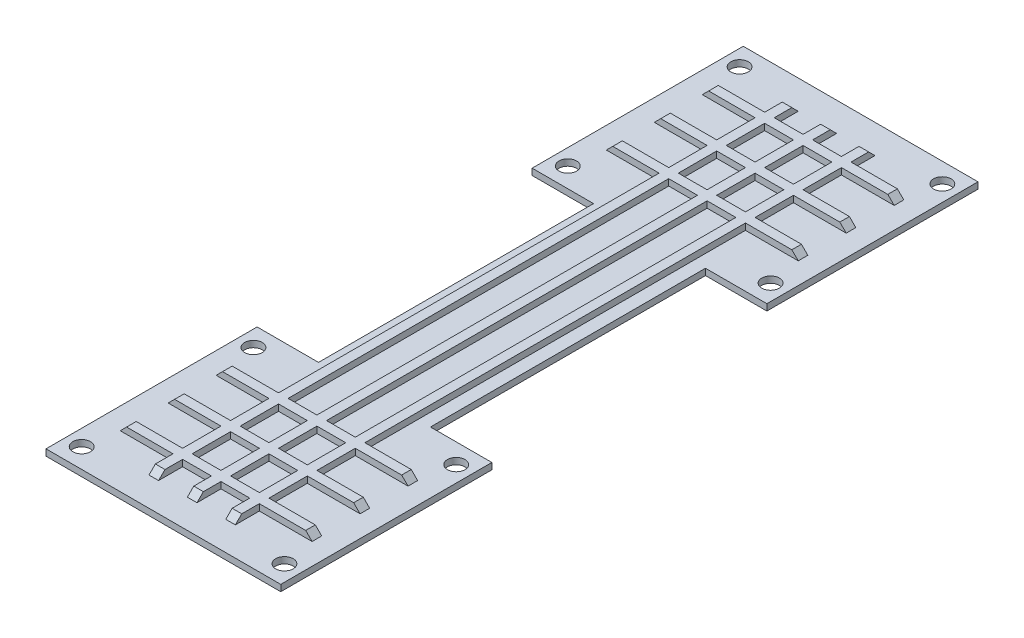
SolidWorks part; units mm, degrees
ref_plane "Front Plane" through (0, 0, 0) normal (0, 0, 1) x (1, 0, 0)
ref_plane "Top Plane" through (0, 0, 0) normal (0, 1, 0) x (1, 0, 0)
ref_plane "Right Plane" through (0, 0, 0) normal (1, 0, 0) x (0, 0, -1)
sketch "Sketch1" plane through (0, 0, 0) normal (0, 1, 0) x (1, 0, 0)
  line L0 (0, -76) -> (0, 76) construction
  line L5 (-17.5, 42.995) -> (-17.5, -42.995)
  line L6 (-31.7, -102.855) -> (31.7, -102.855) construction
  line L11 (-31.7, -102.855) -> (-31.7, -49.145) construction
  line L12 (-31.7, -49.145) -> (31.7, -49.145) construction
  line L13 (31.7, -102.855) -> (31.7, -49.145) construction
  line L14 (0, -49.145) -> (0, -102.855) construction
  line L15 (-31.7, -76) -> (31.7, -76) construction
  line L16 (-31.7, 49.145) -> (31.7, 49.145) construction
  line L17 (-31.7, 49.145) -> (-31.7, 102.855) construction
  line L18 (-31.7, 102.855) -> (31.7, 102.855) construction
  line L19 (31.7, 49.145) -> (31.7, 102.855) construction
  line L20 (0, 102.855) -> (0, 49.145) construction
  line L21 (-31.7, 76) -> (31.7, 76) construction
  line L22 (-36.7, -42.995) -> (-17.5, -42.995)
  line L23 (-36.7, -42.995) -> (-36.7, -109.005)
  line L24 (-36.7, -109.005) -> (36.7, -109.005)
  line L25 (36.7, -42.995) -> (36.7, -109.005)
  line L26 (0, -109.005) -> (0, -32.2076) construction
  line L27 (-36.7, -76) -> (36.7, -76) construction
  line L28 (-36.7, 42.995) -> (-17.5, 42.995)
  line L29 (-36.7, 42.995) -> (-36.7, 109.005)
  line L30 (-36.7, 109.005) -> (36.7, 109.005)
  line L31 (36.7, 42.995) -> (36.7, 109.005)
  line L32 (0, 109.005) -> (0, 37.2379) construction
  line L33 (-36.7, 76) -> (36.7, 76) construction
  line L34 (17.5, -42.995) -> (17.5, 42.995)
  line L35 (17.5, 42.995) -> (36.7, 42.995)
  line L36 (17.5, -42.995) -> (36.7, -42.995)
  circle A4 centre (-31.7, 102.855) radius 2.75
  circle A5 centre (-31.7, 49.145) radius 2.75
  circle A6 centre (31.7, 49.145) radius 2.75
  circle A7 centre (31.7, 102.855) radius 2.75
  circle A8 centre (31.7, -102.855) radius 2.75
  circle A9 centre (31.7, -49.145) radius 2.75
  circle A10 centre (-31.7, -49.145) radius 2.75
  circle A11 centre (-31.7, -102.855) radius 2.75
  point P2 (0, 0)
  point P93 (0, -76)
  point P121 (0, 76)
  point P131 (0, 76)
  point P202 (0, -76)
  dimension "D5" = 5.5
  dimension "D6" = 5.5
  dimension "D7" = 5.5
  dimension "D8" = 5.5
  dimension "D9" = 5.5
  dimension "D10" = 5.5
  dimension "D11" = 5.5
  dimension "D12" = 5.5
  dimension "D1" = 152
  dimension "D2" = 63.4
  dimension "D3" = 53.71
  dimension "D4" = 53.71
  dimension "D13" = 73.4
  dimension "D14" = 66.01
  dimension "D15" = 66.01
  dimension "D16" = 35
extrude "Boss-Extrude1" add sketch "Sketch1" along normal blind 2
sketch "Sketch2" plane through (0, 2, 0) normal (0, 1, 0) x (1, 0, 0)
  line L5 (13.5, 0) -> (10.5, 0)
  line L6 (13.5, 0) -> (13.5, -100)
  line L11 (13.5, -100) -> (10.5, -100)
  line L12 (10.5, 0) -> (10.5, -100)
  line L17 (12, -100) -> (12, 0) construction
  line L18 (13.5, -50) -> (10.5, -50) construction
  line L19 (1.5, 0) -> (-1.5, 0)
  line L20 (1.5, 0) -> (1.5, -100)
  line L21 (1.5, -100) -> (-1.5, -100)
  line L22 (-1.5, 0) -> (-1.5, -100)
  line L23 (0, -100) -> (0, 0) construction
  line L24 (1.5, -50) -> (-1.5, -50) construction
  line L25 (-10.5, 0) -> (-13.5, 0)
  line L26 (-10.5, 0) -> (-10.5, -100)
  line L27 (-10.5, -100) -> (-13.5, -100)
  line L28 (-13.5, 0) -> (-13.5, -100)
  line L29 (-12, -100) -> (-12, 0) construction
  line L30 (-10.5, -50) -> (-13.5, -50) construction
  point P81 (12, -50)
  point P103 (-12, -50)
  point P117 (0, -50)
  dimension "D1" = 3
  dimension "D2" = 3
  dimension "D3" = 3
  dimension "D4" = 100
  dimension "D5" = 12
  dimension "D6" = 12
extrude "Boss-Extrude2" add sketch "Sketch2" along normal blind 2
sketch "Sketch3" plane through (0, 2, 0) normal (0, 1, 0) x (1, 0, 0)
  line L0 (-36.7, -76) -> (36.7, -76) construction
  line L1 (-36.7, -42.995) -> (-36.7, -109.005) construction
  line L2 (36.7, -109.005) -> (36.7, -42.995) construction
  line L4 (-30, -89.5) -> (30, -89.5)
  line L5 (-30, -89.5) -> (-30, -92.5)
  line L6 (-30, -92.5) -> (30, -92.5)
  line L7 (30, -89.5) -> (30, -92.5)
  line L8 (0, -92.5) -> (0, -89.5) construction
  line L9 (-30, -91) -> (30, -91) construction
  line L10 (-30, -59.5) -> (30, -59.5)
  line L11 (-30, -59.5) -> (-30, -62.5)
  line L12 (-30, -62.5) -> (30, -62.5)
  line L13 (30, -59.5) -> (30, -62.5)
  line L14 (0, -62.5) -> (0, -59.5) construction
  line L15 (-30, -61) -> (30, -61) construction
  line L16 (-30, -74.5) -> (30, -74.5)
  line L17 (-30, -74.5) -> (-30, -77.5)
  line L18 (-30, -77.5) -> (30, -77.5)
  line L19 (30, -74.5) -> (30, -77.5)
  line L20 (0, -77.5) -> (0, -74.5) construction
  line L21 (-30, -76) -> (30, -76) construction
  point P16 (0, -76)
  point P87 (0, -76)
  point P112 (0, -61)
  point P122 (0, -91)
  dimension "D1" = 3
  dimension "D2" = 3
  dimension "D3" = 15
  dimension "D4" = 15
  dimension "D5" = 3
  dimension "D6" = 60
extrude "Boss-Extrude3" add sketch "Sketch3" along normal up to surface (2 mm away) up to face at (0, 4, 50)
chamfer "Chamfer1" distance 2 9 edges at (30, 4, 61) (30, 4, 76) (30, 4, 91) (12, 4, 100) (0, 4, 100) (-12, 4, 100) (-30, 4, 91) (-30, 4, 76) (-30, 4, 61)
mirror "Mirror1" about plane through (0, 0, 0) normal (0, 0, 1) of "Chamfer1", "Boss-Extrude3", "Boss-Extrude2"
ref_plane "Plane1" through (0, 0, 0) normal (1, 0, 0) x (0, 0, -1)
equation "\"Reikä\"= 5.5"
equation "\"D5@Sketch1\"=\"Reikä\""
equation "\"D6@Sketch1\"=\"Reikä\""
equation "\"D7@Sketch1\"=\"Reikä\""
equation "\"D8@Sketch1\"=\"Reikä\""
equation "\"D9@Sketch1\"=\"Reikä\""
equation "\"D10@Sketch1\"=\"Reikä\""
equation "\"D11@Sketch1\"=\"Reikä\""
equation "\"D12@Sketch1\"=\"Reikä\""
